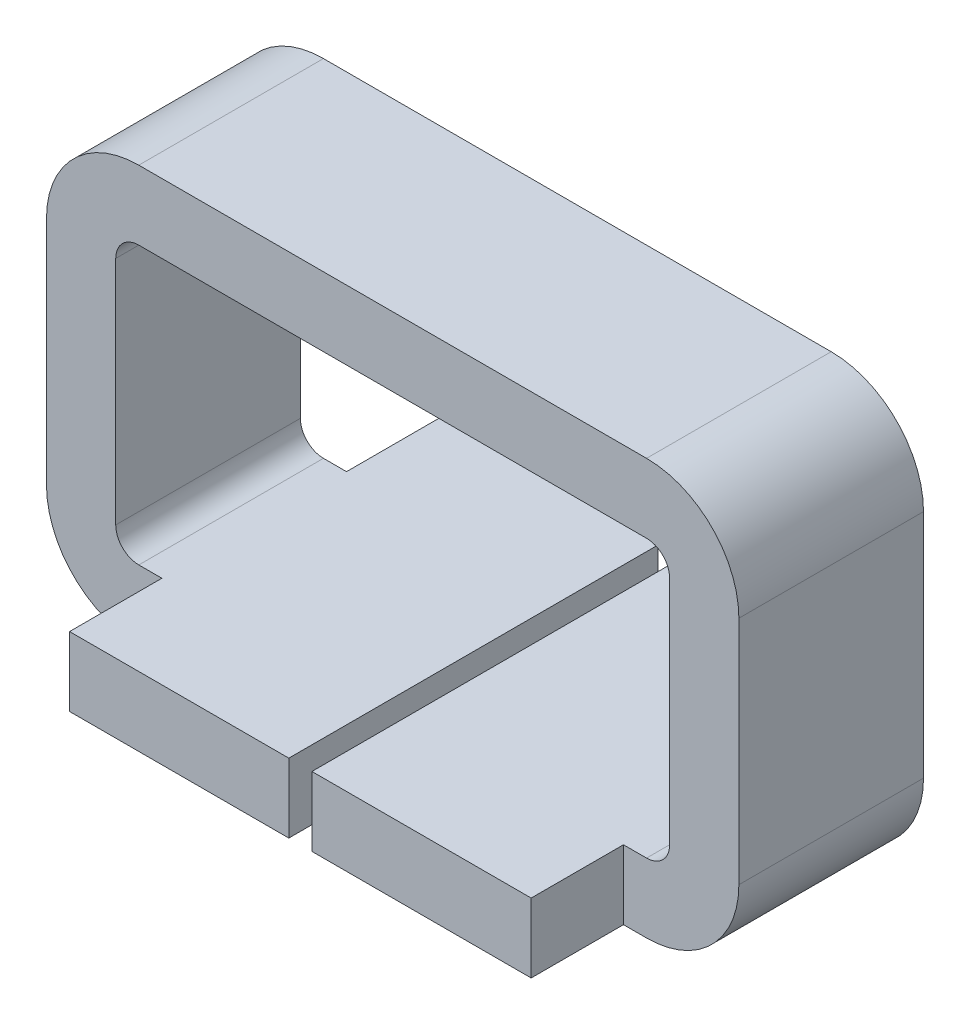
SolidWorks part; units mm, degrees
ref_plane "Front Plane" through (0, 0, 0) normal (0, 0, 1) x (1, 0, 0)
ref_plane "Top Plane" through (0, 0, 0) normal (0, 1, 0) x (1, 0, 0)
ref_plane "Right Plane" through (0, 0, 0) normal (1, 0, 0) x (0, 0, -1)
sketch "Sketch1" plane through (0, 0, 0) normal (0, 0, 1) x (1, 0, 0)
  line L0 (-1.397, 1.905) -> (1.397, 1.905)
  line L1 (-1.397, 2.286) -> (1.397, 2.286)
  line L2 (-1.905, 1.778) -> (-1.905, 0.508)
  line L3 (-1.397, 0) -> (1.397, 0)
  line L4 (1.905, 1.778) -> (1.905, 0.508)
  line L5 (1.524, 1.778) -> (1.524, 0.508)
  line L6 (-1.397, 0.381) -> (1.397, 0.381)
  line L7 (-1.524, 1.778) -> (-1.524, 0.508)
  arc A0 (1.397, 2.286) -> (1.905, 1.778) centre (1.397, 1.778) cw
  arc A1 (1.905, 0.508) -> (1.397, 0) centre (1.397, 0.508) cw
  arc A2 (-1.397, 0) -> (-1.905, 0.508) centre (-1.397, 0.508) cw
  arc A3 (-1.905, 1.778) -> (-1.397, 2.286) centre (-1.397, 1.778) cw
  arc A4 (1.397, 1.905) -> (1.524, 1.778) centre (1.397, 1.778) cw
  arc A5 (1.524, 0.508) -> (1.397, 0.381) centre (1.397, 0.508) cw
  arc A6 (-1.397, 0.381) -> (-1.524, 0.508) centre (-1.397, 0.508) cw
  arc A7 (-1.524, 1.778) -> (-1.397, 1.905) centre (-1.397, 1.778) cw
  point P7 (1.905, 2.286)
  point P10 (1.905, 0)
  point P13 (-1.905, 0)
  dimension "D3" = 0.508
  dimension "D1" = 3.81
  dimension "D2" = 2.286
  dimension "D4" = 0.381
extrude "Boss-Extrude1" add sketch "Sketch1" along normal blind 0.508 and the other way blind 0.508
sketch "Sketch2" plane through (0, 0, 0) normal (0, -1, 0) x (1, 0, 0)
  line L1 (1.27, -1.016) -> (-1.27, -1.016)
  line L2 (1.27, -1.016) -> (1.27, 1.016)
  line L3 (1.27, 1.016) -> (-1.27, 1.016)
  line L4 (-1.27, -1.016) -> (-1.27, 1.016)
  line L5 (1.27, -1.016) -> (-1.27, 1.016) construction
  line L6 (1.27, 1.016) -> (-1.27, -1.016) construction
  point P0 (0, 0)
  dimension "D1" = 2.032
  dimension "D2" = 2.54
extrude "Boss-Extrude2" add sketch "Sketch2" against normal up to surface (0.381 mm away) up to face at (0, 0.381, 0)
sketch "Sketch3" plane through (0, 0, 0) normal (0, -1, 0) x (1, 0, 0)
  line L0 (1.27, 1.016) -> (-1.27, 1.016) construction
  line L1 (0.0635, -1.016) -> (-0.0635, -1.016)
  line L2 (0.0635, -1.016) -> (0.0635, 1.016)
  line L3 (0.0635, 1.016) -> (-0.0635, 1.016)
  line L4 (-0.0635, -1.016) -> (-0.0635, 1.016)
  line L5 (0.0635, -1.016) -> (-0.0635, 1.016) construction
  line L6 (0.0635, 1.016) -> (-0.0635, -1.016) construction
  point P0 (0, 0)
  dimension "D1" = 0.127
extrude "Cut-Extrude1" cut sketch "Sketch3" against normal blind 0.508
